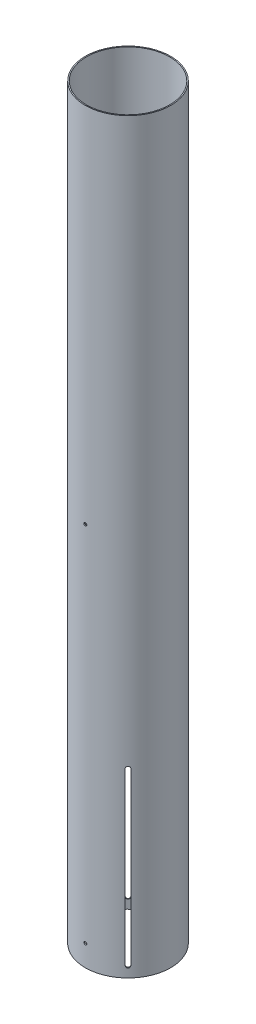
SolidWorks part; units mm, degrees
material "Wildman Fiberglass"
ref_plane "Front Plane" through (0, 0, 0) normal (0, 0, 1) x (1, 0, 0)
ref_plane "Top Plane" through (0, 0, 0) normal (0, 1, 0) x (1, 0, 0)
ref_plane "Right Plane" through (0, 0, 0) normal (1, 0, 0) x (0, 0, -1)
sketch "Sketch1" plane through (0, 0, 0) normal (0, 1, 0) x (1, 0, 0)
  circle A0 centre (0, 0) radius 49.53
  circle A1 centre (0, 0) radius 50.8
  dimension "D1" = 101.6
  dimension "D2" = 99.06
extrude "Boss-Extrude1" add sketch "Sketch1" along normal blind 889
extrude "Cut-Extrude1" cut sketch "Sketch2" against normal blind 152.4
sketch "Sketch2" plane through (1.0217, 1243.3556, -179.1581) normal (0.7071, 0, -0.7071) x (0, 1, 0)
  line L0 (-1230.6556, 128.3427) -> (-1027.4556, 128.3427)
  line L1 (-1027.4556, 123.5802) -> (-1230.6556, 123.5802)
  arc A0 (-1230.6556, 128.3427) -> (-1230.6556, 123.5802) centre (-1230.6556, 125.9615) ccw
  arc A1 (-1027.4556, 128.3427) -> (-1027.4556, 123.5802) centre (-1027.4556, 125.9615) cw
pattern_circular "CirPattern1" count 4 over 360 about axis through (0, 889, 0) along (0, -1, 0) of "Cut-Extrude1" reverse direction yes
extrude "Cut-Extrude2" cut sketch "Sketch3" against normal blind 11.684
sketch "Sketch3" plane through (271.0916, 1243.3556, 52.3875) normal (0, 0, 1) x (-1, 0, 0)
  circle A0 centre (271.0916, 1217.9556) radius 1.7653
  circle A2 centre (271.0916, 786.1556) radius 1.7653
equation "\"Length\"=35"
equation "\"D1@Boss-Extrude1\"=\"Length\""
